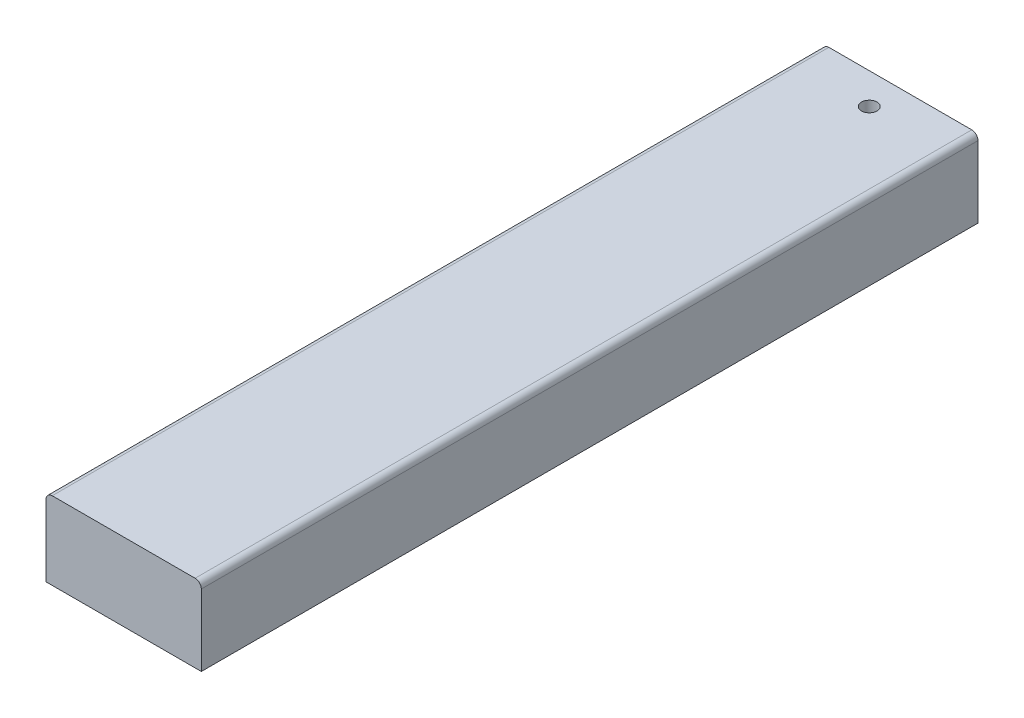
SolidWorks part; units mm, degrees
ref_plane "Front Plane" through (0, 0, 0) normal (0, 0, 1) x (1, 0, 0)
ref_plane "Top Plane" through (0, 0, 0) normal (0, 1, 0) x (1, 0, 0)
ref_plane "Right Plane" through (0, 0, 0) normal (1, 0, 0) x (0, 0, -1)
sketch "Sketch1" plane through (0, 0, 0) normal (0, 0, 1) x (1, 0, 0)
  line L1 (25, -10) -> (-25, -10)
  line L2 (25, -10) -> (25, 10)
  line L3 (25, 10) -> (-25, 10)
  line L4 (-25, -10) -> (-25, 10)
  line L5 (0, 10) -> (0, -10) construction
  line L6 (25, 0) -> (-25, 0) construction
  point P0 (0, 0)
  dimension "D1" = 20
  dimension "D2" = 50
extrude "Boss-Extrude1" add sketch "Sketch1" along normal mid plane 250
sketch "Sketch3" plane through (0, 10, 0) normal (0, 1, 0) x (1, 0, 0)
  line L0 (25, 125) -> (-25, 125) construction
  line L1 (25, 125) -> (-25, 125)
  line L2 (25, 125) -> (25, -125)
  line L3 (25, -125) -> (-25, -125)
  line L4 (-25, 125) -> (-25, -125)
  line L5 (0, -125) -> (0, 125) construction
  line L6 (25, 0) -> (-25, 0) construction
  point P0 (0, 0)
  dimension "D1" = 50
extrude "Boss-Extrude2" add sketch "Sketch3" along normal blind 5
ref_plane "Plane1" through (0, 15, 0) normal (0, 1, 0) x (1, 0, 0)
sketch "Sketch2" plane through (0, 15, 0) normal (0, 1, 0) x (1, 0, 0)
  line L1 (25, 125) -> (-25, 125) construction
  circle A0 centre (0, 115) radius 2.5
  dimension "D1" = 5
  dimension "D2" = 10
extrude "Cut-Extrude1" cut sketch "Sketch2" against normal blind 10 and the other way through all
fillet "Fillet1" radius 2 2 edges at (-25, 15, 0) (25, 15, 0)
sketch "Sketch4" plane through (0, -10, 0) normal (0, -1, 0) x (1, 0, 0)
  line L0 (-25, 125) -> (25, 125) construction
  line L5 (25, 125) -> (25, -125) construction
  circle A0 centre (0, 110) radius 7.874
  dimension "D2" = 15.748
  dimension "D1" = 15
  dimension "D3" = 25
extrude "Cut-Extrude2" cut sketch "Sketch4" against normal blind 10
